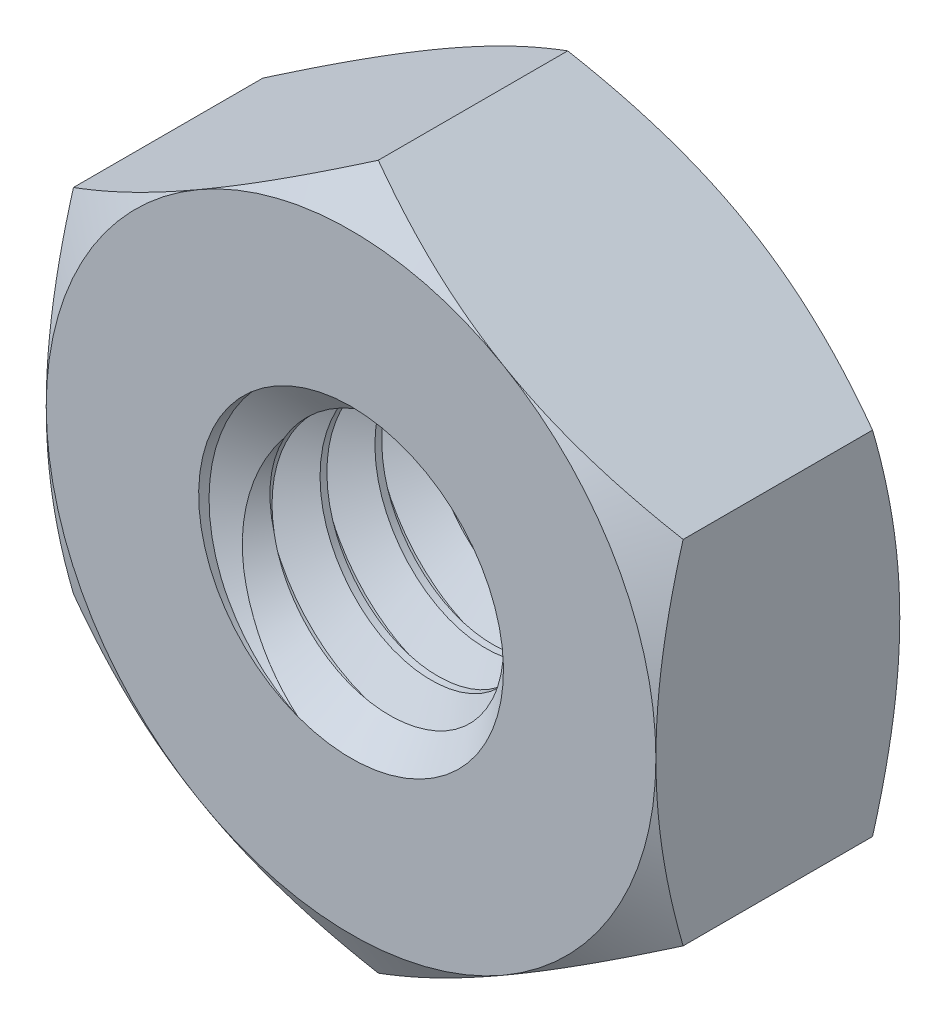
SolidWorks part; units mm, degrees
ref_plane "Front" through (0, 0, 0) normal (0, 0, 1) x (1, 0, 0)
ref_plane "Top" through (0, 0, 0) normal (0, 1, 0) x (1, 0, 0)
ref_plane "Right" through (0, 0, 0) normal (1, 0, 0) x (0, 0, -1)
sketch "Sketch1" plane through (0, 0, 0) normal (0, 0, 1) x (1, 0, 0)
  line L1 (-2.5, 1.4434) -> (-2.5, -1.4434)
  line L2 (-2.5, -1.4434) -> (0, -2.8868)
  line L3 (0, -2.8868) -> (2.5, -1.4434)
  line L4 (2.5, -1.4434) -> (2.5, 1.4434)
  line L5 (2.5, 1.4434) -> (0, 2.8868)
  line L6 (0, 2.8868) -> (-2.5, 1.4434)
  circle A0 centre (0, 0) radius 2.5 construction
  circle A1 centre (0, 0) radius 1.25 construction
  point P10 (0, 1.25)
  dimension "hex" = 5
  dimension "dia" = 2.5
extrude "Extrude1" add sketch "Sketch1" along normal mid plane 2
sketch "Sketch4" plane through (0, 0, -1) normal (0, 0, -1) x (-1, 0, 0)
  circle A0 centre (0, 0) radius 1.25 construction
  circle A1 centre (0, 0) radius 1.25
sketch "Sketch10" plane through (0, 0, 1) normal (0, 0, 1) x (1, 0, 0)
  circle A0 centre (0, 0) radius 1.25 construction
  circle A1 centre (0, 0) radius 1.25
extrude "Cut-Extrude2" cut sketch "Sketch10" against normal through all draft 45
sketch "Sketch11" plane through (0, 0, -1) normal (0, 0, -1) x (-1, 0, 0)
  circle A0 centre (0, 0) radius 1.25 construction
  circle A1 centre (0, 0) radius 1.25
extrude "Cut-Extrude3" cut sketch "Sketch11" against normal through all draft 45
sketch "Sketch13" plane through (0, 0, -1) normal (0, 0, -1) x (-1, 0, 0)
  circle A0 centre (0, 0) radius 1.25 construction
  circle A1 centre (0, 0) radius 1.25
extrude "Boss-Extrude1" add sketch "Sketch13" against normal up to vertex (2 mm away) separate body up to point (-2.5, 1.4434, 1)
curve "Helix/Spiral3" pitch 0.45 height 2 turns 4.4444
sketch "Sketch12" plane through (0, 0, 0) normal (1, 0, 0) x (0, 0, -1)
  line L0 (1.3938, 1.25) -> (1, 1.25)
  line L1 (1.3938, 1.25) -> (1.225, 0.9577)
  line L2 (1.225, 0.9577) -> (1.1688, 0.9577)
  line L3 (1.1688, 0.9577) -> (1, 1.25)
  line L4 (1.1969, 0.9577) -> (1.1969, 1.25) construction
  line L5 (1.0844, 1.1039) -> (1.3094, 1.1039) construction
  dimension "D1" = 60
  dimension "D2" = 0.0563
  dimension "D3" = 0.225
sweep "Cut-Sweep1" cut profiles "Sketch12" path "Helix/Spiral3"
combine bodies "Combine1" operation type subtract main body 116 bodies to subtract 118
sketch "Sketch7" plane through (0, 0, 1) normal (0, 0, 1) x (1, 0, 0)
  circle A0 centre (0, 0) radius 2.5 construction
  circle A1 centre (0, 0) radius 2.5
extrude "Extrude2" cut sketch "Sketch7" against normal blind 25.4 draft 60 flip side to cut
mirror "Mirror2" about plane through (0, 0, 0) normal (0, 0, 1) of "Extrude2"
sketch "Sketch8" plane through (0, 0, 1) normal (0, 0, 1) x (1, 0, 0)
  line L0 (-0.8839, 0.8839) -> (0, 0) construction
  line L1 (0, -1.2361) -> (0, 1.2361) construction
  circle A1 centre (0, 0) radius 1.25 construction
  point P0 (-0.8839, 0.8839)
  dimension "D1" = 45
sketch "Sketch14" plane through (0, 0, 1) normal (0, 0, 1) x (1, 0, 0)
  line L0 (0, 0) -> (-1.25, 0) construction
  arc A0 (0, 1.25) -> (-0.4358, -1.1716) centre (0, 0) ccw construction
equation "\"D3@Helix/Spiral3\" = \"length@Extrude1\" "
equation "\"D2@Sketch12\" = \"D4@Helix/Spiral3\"*.125"
equation "\"D3@Sketch12\" = \"D4@Helix/Spiral3\"*.50"
